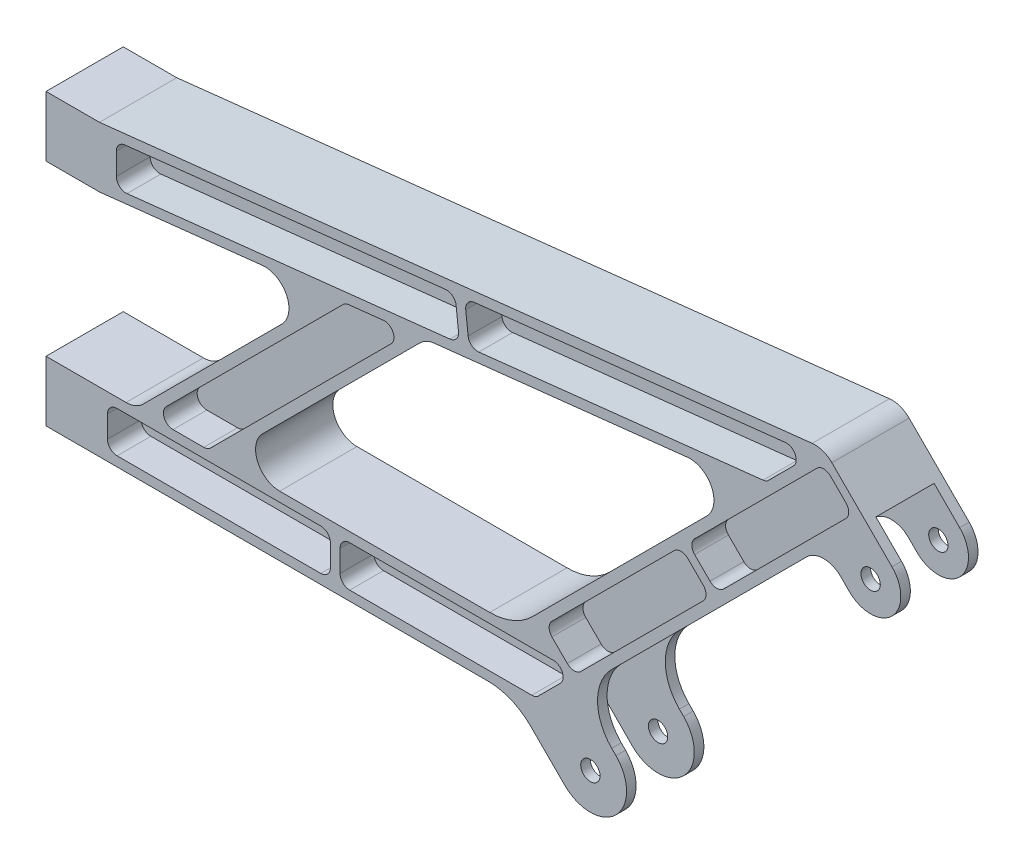
SolidWorks part; units mm, degrees
material "6061-T6 (SS)"
ref_plane "Front Plane" through (0, 0, 0) normal (0, 0, 1) x (1, 0, 0)
ref_plane "Top Plane" through (0, 0, 0) normal (0, 1, 0) x (1, 0, 0)
ref_plane "Right Plane" through (0, 0, 0) normal (1, 0, 0) x (0, 0, -1)
sketch "Sketch1" plane through (0, 0, 0) normal (0, 0, 1) x (1, 0, 0)
  line L1 (-157.7639, -90.8401) -> (-244.7728, -90.8401)
  line L2 (-67.8181, -11.2496) -> (-140.0863, -83.5177)
  line L3 (-16.0497, 33.7315) -> (8.8396, 8.8381)
  line L4 (-12.3744, -5.3033) -> (-8.8388, -8.8388)
  line L5 (-26.5165, -5.3033) -> (-107.2487, -86.0355)
  line L6 (-140.8326, -123.1624) -> (-126.6942, -137.3008)
  line L7 (-158.5102, -115.8401) -> (-341.1373, -115.8401)
  line L8 (-341.1373, -115.8401) -> (-341.1373, -90.8401)
  line L9 (-308.4124, -90.8401) -> (-341.1373, -90.8401)
  line L11 (-341.5776, -20.8403) -> (-319.4176, -20.8403)
  line L12 (-341.5776, -20.8403) -> (-341.5776, 4.1597)
  line L13 (-341.5776, 4.1597) -> (-319.4176, 4.1597)
  line L14 (-107.2487, -114.3198) -> (-105.481, -116.0876)
  line L15 (-319.4176, 4.1597) -> (-24.2138, 36.6012)
  line L17 (-301.3413, -87.9111) -> (-243.8773, -30.4471)
  line L18 (-75.9816, 5.7616) -> (-180.7131, -5.7479)
  line L19 (-251.8438, -73.769) -> (-186.6918, -8.6169)
  line L20 (-252.0407, -13.4359) -> (-319.4176, -20.8403)
  arc A4 (8.8388, -8.8388) -> (8.8396, 8.8381) centre (0, 0) ccw
  arc A5 (-8.8388, -8.8388) -> (8.8388, -8.8388) centre (0, 0) ccw
  arc A6 (-12.3744, -5.3033) -> (-26.5165, -5.3033) centre (-19.4454, -12.3744) ccw
  arc A7 (-107.2487, -86.0355) -> (-107.2487, -114.3198) centre (-93.1066, -100.1777) ccw
  arc A8 (-105.481, -137.3008) -> (-105.481, -116.0876) centre (-116.0876, -126.6942) ccw
  arc A9 (-126.6942, -137.3008) -> (-105.481, -137.3008) centre (-116.0876, -126.6942) ccw
  circle A12 centre (-116.0876, -126.6942) radius 4
  circle A13 centre (0, 0) radius 4
  arc A15 (-158.5102, -115.8401) -> (-140.8326, -123.1624) centre (-158.5102, -140.8401) cw
  arc A16 (-157.7639, -90.8401) -> (-140.0863, -83.5177) centre (-157.7639, -65.8401) ccw
  arc A20 (-67.8181, -11.2496) -> (-75.9816, 5.7616) centre (-74.8892, -4.1785) ccw
  arc A21 (-16.0497, 33.7315) -> (-24.2138, 36.6012) centre (-23.1214, 26.661) ccw
  arc A22 (-186.6918, -8.6169) -> (-180.7131, -5.7479) centre (-179.6207, -15.688) cw
  arc A23 (-244.7728, -90.8401) -> (-251.8438, -73.769) centre (-244.7728, -80.8401) cw
  arc A25 (-308.4124, -90.8401) -> (-301.3413, -87.9111) centre (-308.4124, -80.8401) ccw
  arc A26 (-252.0407, -13.4359) -> (-243.8773, -30.4471) centre (-250.9484, -23.3761) cw
  dimension "D2" = 25
  dimension "D3" = 25
  dimension "D7" = 10
  dimension "D9" = 22.16
  dimension "D6" = 25
  dimension "D1" = 25
  dimension "D4" = 25
  dimension "D5" = 25
  dimension "D8" = 119.9998
extrude "Boss-Extrude1" add sketch "Sketch1" along normal blind 32
sketch "Sketch2" plane through (0, 0, 32) normal (0, 0, 1) x (1, 0, 0)
  line L0 (-107.2487, -86.0355) -> (-26.5165, -5.3033) construction
  line L1 (-137.5386, -110.6685) -> (-128.5386, -101.6685)
  line L2 (-131.367, -94.8401) -> (-215.77, -94.8401)
  line L3 (-67.8181, -11.2496) -> (-140.0863, -83.5177) construction
  line L4 (-107.2487, -86.0355) -> (-26.5165, -5.3033)
  line L5 (-67.8181, -11.2496) -> (-140.0863, -83.5177)
  line L6 (-22.272, 28.6397) -> (-72.893, -21.9813)
  line L7 (-119.9767, -93.1066) -> (-69.3575, -42.4874)
  line L8 (-131.9975, -86.7426) -> (-125.6335, -93.1066)
  line L9 (-10.2515, 22.275) -> (-16.6149, 28.6394)
  line L10 (-64.9897, -14.078) -> (-137.2579, -86.3462) construction
  line L11 (-110.0772, -83.2071) -> (-29.3449, -2.4749) construction
  line L12 (-341.1373, -115.8401) -> (-158.5102, -115.8401) construction
  line L13 (-341.1373, -115.8401) -> (-158.5102, -115.8401)
  line L14 (-312.1373, -111.8401) -> (-227.77, -111.8401)
  line L15 (-341.1373, -111.8401) -> (-158.5102, -111.8401) construction
  line L16 (-341.1373, -90.8401) -> (-341.1373, -115.8401) construction
  line L17 (-316.1373, -98.8401) -> (-316.1373, -107.8401)
  line L18 (-157.7639, -90.8401) -> (-244.7728, -90.8401) construction
  line L19 (8.8396, 8.8381) -> (-16.0497, 33.7315) construction
  line L20 (-140.8326, -123.1624) -> (-126.6942, -137.3008) construction
  line L21 (-65.1149, -38.2448) -> (-77.1357, -26.224) construction
  line L22 (-72.893, -27.6382) -> (-66.5291, -34.0022)
  line L23 (-75.7215, -30.4666) -> (-69.3575, -36.8306)
  line L24 (-81.3783, -30.4666) -> (-131.9975, -81.0858)
  line L25 (-60.8722, -34.0022) -> (-10.2517, 16.6183)
  line L26 (-221.77, -94.8401) -> (-221.77, -111.8401) construction
  line L27 (-219.77, -98.8401) -> (-219.77, -107.8401)
  line L28 (-223.77, -98.8401) -> (-223.77, -107.8401)
  line L29 (-215.77, -111.8401) -> (-140.367, -111.8401)
  line L30 (-227.77, -94.8401) -> (-312.1373, -94.8401)
  line L38 (-308.8907, 1.2925) -> (-176.1091, 15.8845)
  line L39 (-24.2138, 36.6012) -> (-319.4176, 4.1597) construction
  line L40 (-308.0168, -15.7138) -> (-174.2521, -1.0137)
  line L41 (-75.9816, 5.7616) -> (-180.7131, -5.7479) construction
  line L42 (-312.4538, -2.6836) -> (-312.4538, -11.7378)
  line L43 (-32.0118, 24.5568) -> (-42.1838, 14.3847)
  line L44 (-170.145, 16.5399) -> (-168.288, -0.3583) construction
  line L45 (-171.6961, 12.3454) -> (-170.713, 3.3993)
  line L46 (-167.7201, 12.7824) -> (-166.7369, 3.8362)
  line L47 (-164.181, 17.1954) -> (-35.2771, 31.3613)
  line L48 (-162.3239, 0.2971) -> (-44.5753, 13.2371)
  line L49 (-218.5658, -10.7925) -> (-291.7849, -84.0116)
  line L50 (-243.8773, -30.4471) -> (-301.3413, -87.9111) construction
  line L51 (-198.6096, -14.8779) -> (-273.4002, -89.6685)
  line L52 (-186.6918, -8.6169) -> (-251.8438, -73.769) construction
  line L53 (-216.1743, -9.6449) -> (-201.875, -8.0734)
  line L54 (-288.9565, -90.8401) -> (-276.2286, -90.8401)
  line L55 (-341.5776, 4.1597) -> (-341.5776, -20.8403) construction
  arc A0 (-22.272, 28.6397) -> (-16.6149, 28.6394) centre (-19.4436, 25.8113) cw
  arc A1 (-10.2517, 16.6183) -> (-10.2515, 22.275) centre (-13.0801, 19.4468) ccw
  arc A2 (-119.9767, -93.1066) -> (-125.6335, -93.1066) centre (-122.8051, -90.2782) cw
  arc A3 (-131.9975, -81.0858) -> (-131.9975, -86.7426) centre (-129.169, -83.9142) ccw
  arc A4 (-312.1373, -111.8401) -> (-316.1373, -107.8401) centre (-312.1373, -107.8401) cw
  arc A5 (-312.1373, -94.8401) -> (-316.1373, -98.8401) centre (-312.1373, -98.8401) ccw
  arc A6 (-140.367, -111.8401) -> (-137.5386, -110.6685) centre (-140.367, -107.8401) ccw
  arc A7 (-128.5386, -101.6685) -> (-131.367, -94.8401) centre (-131.367, -98.8401) ccw
  arc A8 (-75.7215, -30.4666) -> (-81.3783, -30.4666) centre (-78.5499, -33.295) ccw
  arc A9 (-69.3575, -36.8306) -> (-69.3575, -42.4874) centre (-72.1859, -39.659) cw
  arc A10 (-66.5291, -34.0022) -> (-60.8722, -34.0022) centre (-63.7006, -31.1737) ccw
  arc A11 (-72.893, -27.6382) -> (-72.893, -21.9813) centre (-70.0646, -24.8098) cw
  arc A12 (-223.77, -107.8401) -> (-227.77, -111.8401) centre (-227.77, -107.8401) cw
  arc A13 (-219.77, -107.8401) -> (-215.77, -111.8401) centre (-215.77, -107.8401) ccw
  arc A14 (-219.77, -98.8401) -> (-215.77, -94.8401) centre (-215.77, -98.8401) cw
  arc A15 (-223.77, -98.8401) -> (-227.77, -94.8401) centre (-227.77, -98.8401) ccw
  arc A20 (-44.5753, 13.2371) -> (-42.1838, 14.3847) centre (-45.0122, 17.2132) ccw
  arc A21 (-35.2771, 31.3613) -> (-32.0118, 24.5568) centre (-34.8402, 27.3852) cw
  arc A22 (-166.7369, 3.8362) -> (-162.3239, 0.2971) centre (-162.7609, 4.2732) ccw
  arc A23 (-167.7201, 12.7824) -> (-164.181, 17.1954) centre (-163.744, 13.2193) cw
  arc A24 (-170.713, 3.3993) -> (-174.2521, -1.0137) centre (-174.6891, 2.9623) cw
  arc A25 (-171.6961, 12.3454) -> (-176.1091, 15.8845) centre (-175.6722, 11.9085) ccw
  arc A26 (-308.0168, -15.7138) -> (-312.4538, -11.7378) centre (-308.4538, -11.7378) cw
  arc A27 (-308.8907, 1.2925) -> (-312.4538, -2.6836) centre (-308.4538, -2.6836) ccw
  arc A28 (-198.6096, -14.8779) -> (-201.875, -8.0734) centre (-201.438, -12.0495) ccw
  arc A29 (-218.5658, -10.7925) -> (-216.1743, -9.6449) centre (-215.7374, -13.6209) cw
  arc A30 (-273.4002, -89.6685) -> (-276.2286, -90.8401) centre (-276.2286, -86.8401) cw
  arc A31 (-288.9565, -90.8401) -> (-291.7849, -84.0116) centre (-288.9565, -86.8401) cw
  point P34 (-316.1373, -111.8401)
  point P53 (-78.5499, -27.6382)
  point P58 (-63.7006, -36.8306)
  point P69 (-223.77, -111.8401)
  point P72 (-219.77, -111.8401)
  point P75 (-219.77, -94.8401)
  point P78 (-223.77, -94.8401)
  point P117 (-166.3, -0.1398)
  point P120 (-168.157, 16.7584)
  point P123 (-170.276, -0.5768)
  point P126 (-172.1331, 16.3215)
  dimension "D2" = 4
  dimension "D6" = 4
  dimension "D11" = 4
  dimension "D13" = 4
  dimension "D16" = 4
  dimension "D22" = 4
  dimension "D19" = 4
  dimension "D4" = 25
  dimension "D5" = 4
  dimension "D7" = 4
  dimension "D8" = 4
  dimension "D9" = 32
  dimension "D10" = 2
  dimension "D12" = 2
  dimension "D14" = 4
  dimension "D15" = 4
  dimension "D17" = 4
  dimension "D18" = 4
  dimension "D20" = 4
  dimension "D21" = 2
  dimension "D23" = 4
  dimension "D1" = 4
  dimension "D3" = 4
extrude "Cut-Extrude1" cut sketch "Sketch2" against normal blind 14 contours L38 A27 L42 A26 L40 A24 L45 A25 | A23 L46 A22 L48 A20 L43 A21 L47 | A31 L54 A30 L51 A28 L53 A29 L49 | A11 L22 A10 L25 A1 L9 A0 L6 | A9 L23 A8 L24 A3 L8 A2 L7 | A14 L27 A13 L29 A6 L1 A7 L2 | L28 A15 L30 A5 L17 A4 L14 A12 region at (-175.3079, -103.1533, 32) region at (-41.5723, -2.6814, 32) region at (-100.6775, -61.7866, 32) region at (-269.9537, -103.3401, 32) region at (-241.8227, 0.0982, 32) region at (-100.9045, 15.7508, 32) region at (-245.4094, -49.7028, 32)
ref_plane "Plane1" through (0, 0, 16) normal (0, 0, 1) x (1, 0, 0)
mirror "Mirror1" about plane through (0, 0, 16) normal (0, 0, 1) of "Cut-Extrude1"
sketch "Sketch3" plane through (0, 0, 16) normal (0, 0, 1) x (1, 0, 0)
  line L0 (-158.5102, -115.8401) -> (-141.1954, -115.8401)
  line L1 (-98.969, -77.7558) -> (-134.1243, -112.9111)
  line L2 (-107.2487, -86.0355) -> (-26.5165, -5.3033) construction
  line L3 (-158.5102, -115.8401) -> (-116.5971, -149.2186)
  line L4 (-116.5971, -149.2186) -> (-66.3597, -110.0186)
  line L5 (-66.3597, -110.0186) -> (-98.969, -77.7558)
  line L6 (-29.0156, -7.8024) -> (7.8698, 29.083)
  line L7 (7.8698, 29.083) -> (26.3533, -15.3879)
  line L8 (26.3533, -15.3879) -> (-12.041, -17.819)
  line L9 (-12.041, -17.819) -> (-29.0156, -7.8024)
  arc A0 (-134.1243, -112.9111) -> (-141.1954, -115.8401) centre (-141.1954, -105.8401) cw
  dimension "D1" = 10
extrude "Cut-Extrude2" cut sketch "Sketch3" against normal blind 12.0515 and the other way blind 12.0515
sketch "Sketch5" plane through (0, 0, 16) normal (0, 0, 1) x (1, 0, 0)
  line L0 (0, -24.7236) -> (0, -90.9031)
sketch "Sketch6" plane through (-341.1373, 0, 0) normal (-1, 0, 0) x (0, 0, 1)
  line L4 (0, -90.8401) -> (0, -115.8401)
  line L5 (0, -115.8401) -> (32, -115.8401)
  line L6 (32, -115.8401) -> (32, -90.8401)
  line L7 (32, -90.8401) -> (0, -90.8401)
  line L8 (0, -90.8401) -> (0, -115.8401)
  line L9 (0, -115.8401) -> (32, -115.8401)
  line L10 (32, -115.8401) -> (32, -90.8401)
  line L11 (32, -90.8401) -> (0, -90.8401)
  dimension "D1" = 0
extrude "Boss-Extrude2" add sketch "Sketch6" along normal up to surface (0.4403 mm away)
